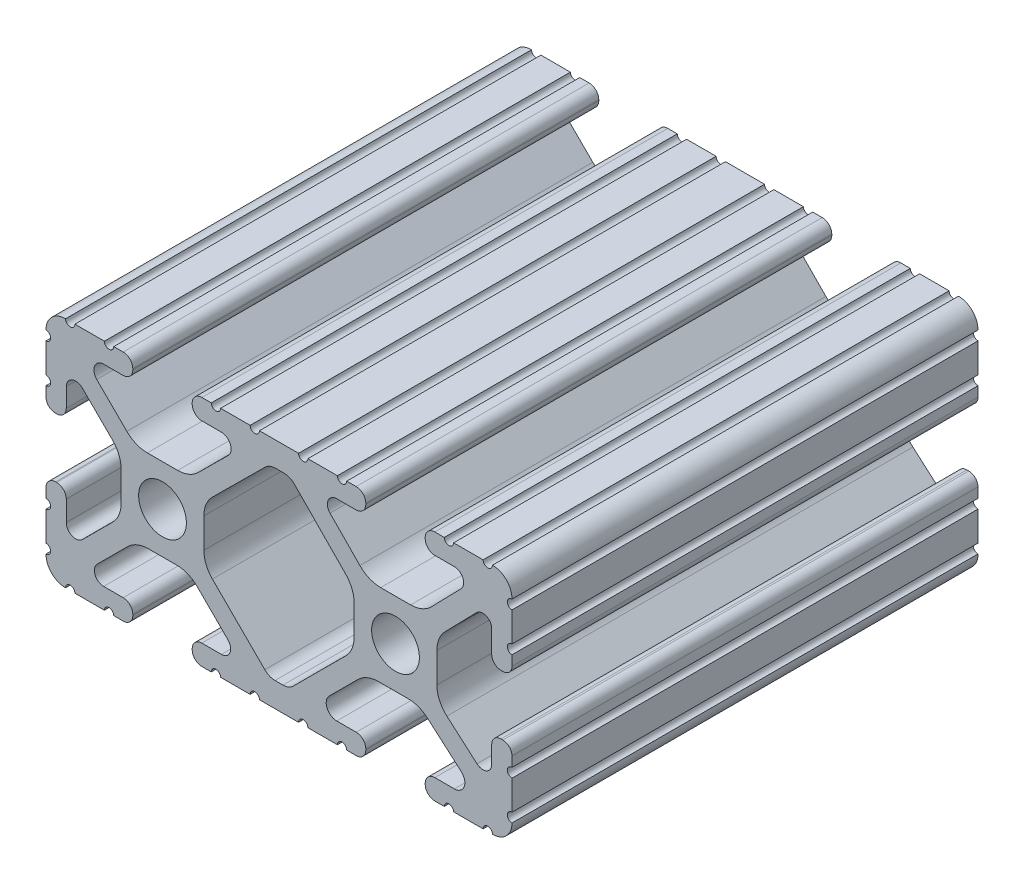
SolidWorks part; units mm, degrees
material "6061 Alloy"
ref_plane "Front Plane" through (0, 0, 0) normal (0, 0, 1) x (1, 0, 0)
ref_plane "Top Plane" through (0, 0, 0) normal (0, 1, 0) x (1, 0, 0)
ref_plane "Right Plane" through (0, 0, 0) normal (1, 0, 0) x (0, 0, -1)
sketch "Sketch1" plane through (0, 0, 0) normal (0, 0, 1) x (1, 0, 0)
  line L0 (-32.9707, 0) -> (32.2708, 0) construction
  line L1 (0, 12.7) -> (0, 0) construction
  line L2 (-12.7, 14.992) -> (-12.7, -12.6999) construction
  line L3 (12.7, 13.9801) -> (12.7, -13.3809) construction
  line L4 (-7.2595, -3.8694) -> (-1.5457, -9.5728)
  line L5 (1.5457, -9.5728) -> (7.2595, -3.8694)
  line L7 (-0.3952, 10.033) -> (0.5515, 10.033)
  line L9 (0.4332, -10.033) -> (-0.4332, -10.033)
  line L12 (8.1915, -1.6223) -> (8.1915, 1.6223)
  line L13 (7.2829, 3.8459) -> (1.6756, 9.5611)
  line L14 (-1.504, 9.5765) -> (-7.252, 3.8768)
  line L15 (-8.1915, 1.6223) -> (-8.1915, -1.6223)
  line L16 (22.2504, 12.7) -> (19.0331, 12.7)
  line L17 (18.0171, 12.7) -> (16.9875, 12.7)
  line L18 (15.9385, 11.651) -> (15.9385, 11.5392)
  line L19 (16.9875, 10.4902) -> (19.1164, 10.4902)
  line L20 (19.8441, 8.7652) -> (16.619, 5.4551)
  line L21 (14.3449, 4.4958) -> (11.0833, 4.4958)
  line L22 (8.817, 5.4472) -> (5.5642, 8.7627)
  line L23 (6.2894, 10.4902) -> (8.4125, 10.4902)
  line L24 (9.4615, 11.5392) -> (9.4615, 11.651)
  line L25 (8.4125, 12.7) -> (7.3829, 12.7)
  line L26 (6.3669, 12.7) -> (3.1496, 12.7)
  line L27 (2.1336, 12.7) -> (-2.1336, 12.7)
  line L28 (-3.1496, 12.7) -> (-6.3669, 12.7)
  line L29 (-7.3829, 12.7) -> (-8.4125, 12.7)
  line L30 (-9.4615, 11.651) -> (-9.4615, 11.5392)
  line L31 (-8.4125, 10.4902) -> (-6.2836, 10.4902)
  line L32 (-5.5326, 8.6661) -> (-8.81, 5.4163)
  line L33 (-11.0455, 4.4958) -> (-14.3545, 4.4958)
  line L34 (-16.59, 5.4163) -> (-19.8674, 8.6661)
  line L35 (-19.1164, 10.4902) -> (-16.9875, 10.4902)
  line L36 (-15.9385, 11.5392) -> (-15.9385, 11.651)
  line L37 (-16.9875, 12.7) -> (-18.0171, 12.7)
  line L38 (-19.0331, 12.7) -> (-22.2504, 12.7)
  line L39 (-25.4, 9.5504) -> (-25.4, 6.3331)
  line L40 (-25.4, 5.3171) -> (-25.4, 4.2375)
  line L41 (-24.401, 3.2385) -> (-24.2392, 3.2385)
  line L42 (-23.1902, 4.2875) -> (-23.1902, 6.3347)
  line L43 (-21.434, 7.0665) -> (-18.148, 3.8082)
  line L44 (-17.2085, 1.5536) -> (-17.2085, -1.6952)
  line L45 (-18.1405, -3.9423) -> (-21.4316, -7.2274)
  line L46 (-23.1902, -6.498) -> (-23.1902, -4.2875)
  line L47 (-24.2392, -3.2385) -> (-24.351, -3.2385)
  line L48 (-25.4, -4.2875) -> (-25.4, -5.3171)
  line L49 (-25.4, -6.3331) -> (-25.4, -9.5504)
  line L50 (-22.2504, -12.7) -> (-19.0331, -12.7)
  line L51 (-18.0171, -12.7) -> (-16.9875, -12.7)
  line L52 (-15.9384, -11.651) -> (-15.9384, -11.5392)
  line L53 (-16.9875, -10.4902) -> (-19.1164, -10.4902)
  line L54 (-19.8341, -8.7551) -> (-16.4966, -5.4237)
  line L55 (-14.2536, -4.4958) -> (-11.1464, -4.4958)
  line L56 (-8.9034, -5.4237) -> (-5.5659, -8.7551)
  line L57 (-6.2836, -10.4902) -> (-8.4125, -10.4902)
  line L58 (-9.4616, -11.5392) -> (-9.4616, -11.651)
  line L59 (-8.4125, -12.7) -> (-7.3829, -12.7)
  line L60 (-6.3669, -12.7) -> (-3.1496, -12.7)
  line L61 (-2.1336, -12.7) -> (2.1336, -12.7)
  line L62 (3.1496, -12.7) -> (6.3669, -12.7)
  line L63 (7.3829, -12.7) -> (8.4125, -12.7)
  line L64 (9.4616, -11.651) -> (9.4616, -11.5392)
  line L65 (8.4125, -10.4902) -> (6.2894, -10.4902)
  line L66 (5.4807, -8.5353) -> (8.5979, -5.4237)
  line L67 (10.8409, -4.4958) -> (14.1026, -4.4958)
  line L68 (16.1879, -5.2766) -> (19.8682, -8.4822)
  line L69 (19.1164, -10.4902) -> (16.9875, -10.4902)
  line L70 (15.9384, -11.5392) -> (15.9384, -11.651)
  line L71 (16.9875, -12.7) -> (18.0171, -12.7)
  line L72 (19.0331, -12.7) -> (22.2504, -12.7)
  line L73 (25.4, -9.5504) -> (25.4, -6.3331)
  line L74 (25.4, -5.3171) -> (25.4, -4.2375)
  line L75 (24.401, -3.2385) -> (24.1892, -3.2385)
  line L76 (23.1902, -4.2375) -> (23.1902, -6.1559)
  line L77 (21.584, -6.8869) -> (18.2982, -4.025)
  line L78 (17.2085, -1.6308) -> (17.2085, 1.6308)
  line L79 (18.1094, 3.8465) -> (21.5263, 7.3534)
  line L80 (23.1902, 6.6769) -> (23.1902, 4.2375)
  line L81 (24.1892, 3.2385) -> (24.401, 3.2385)
  line L82 (25.4, 4.2375) -> (25.4, 5.3171)
  line L83 (25.4, 6.3332) -> (25.4, 9.5504)
  circle A0 centre (-12.7, 0) radius 2.6035
  circle A1 centre (12.7, 0) radius 2.6035
  arc A2 (-0.3952, 10.033) -> (-1.504, 9.5765) centre (-0.3952, 8.4582) ccw
  arc A3 (0.5515, 10.033) -> (1.6756, 9.5611) centre (0.5515, 8.4582) cw
  arc A4 (-8.1915, -1.6223) -> (-7.2595, -3.8694) centre (-5.0165, -1.6223) ccw
  arc A5 (-0.4332, -10.033) -> (-1.5457, -9.5728) centre (-0.4332, -8.4582) cw
  arc A6 (7.2595, -3.8694) -> (8.1915, -1.6223) centre (5.0165, -1.6223) ccw
  arc A7 (8.1915, 1.6223) -> (7.2829, 3.8459) centre (5.0165, 1.6223) ccw
  arc A8 (0.4332, -10.033) -> (1.5457, -9.5728) centre (0.4332, -8.4582) ccw
  arc A9 (-7.252, 3.8768) -> (-8.1915, 1.6223) centre (-5.0165, 1.6223) ccw
  arc A16 (25.3998, 10.5664) -> (23.2664, 12.6998) centre (23.2918, 10.5918) ccw
  arc A17 (22.2504, 12.7) -> (23.2664, 12.6998) centre (22.7584, 12.7) ccw
  arc A18 (18.0171, 12.7) -> (19.0331, 12.7) centre (18.5251, 12.7) ccw
  arc A19 (16.9875, 12.7) -> (15.9385, 11.651) centre (16.9875, 11.651) ccw
  arc A20 (15.9385, 11.5392) -> (16.9875, 10.4902) centre (16.9875, 11.5392) ccw
  arc A21 (19.8441, 8.7652) -> (19.1164, 10.4902) centre (19.1164, 9.4742) ccw
  arc A22 (14.3449, 4.4958) -> (16.619, 5.4551) centre (14.3449, 7.6708) ccw
  arc A23 (8.817, 5.4472) -> (11.0833, 4.4958) centre (11.0833, 7.6708) ccw
  arc A24 (6.2894, 10.4902) -> (5.5642, 8.7627) centre (6.2894, 9.4742) ccw
  arc A25 (8.4125, 10.4902) -> (9.4615, 11.5392) centre (8.4125, 11.5392) ccw
  arc A26 (9.4615, 11.651) -> (8.4125, 12.7) centre (8.4125, 11.651) ccw
  arc A27 (6.3669, 12.7) -> (7.3829, 12.7) centre (6.8749, 12.7) ccw
  arc A28 (2.1336, 12.7) -> (3.1496, 12.7) centre (2.6416, 12.7) ccw
  arc A29 (-3.1496, 12.7) -> (-2.1336, 12.7) centre (-2.6416, 12.7) ccw
  arc A30 (-7.3829, 12.7) -> (-6.3669, 12.7) centre (-6.8749, 12.7) ccw
  arc A31 (-8.4125, 12.7) -> (-9.4615, 11.651) centre (-8.4125, 11.651) ccw
  arc A32 (-9.4615, 11.5392) -> (-8.4125, 10.4902) centre (-8.4125, 11.5392) ccw
  arc A33 (-5.5326, 8.6661) -> (-6.2836, 10.4902) centre (-6.2836, 9.4235) ccw
  arc A34 (-11.0455, 4.4958) -> (-8.81, 5.4163) centre (-11.0455, 7.6708) ccw
  arc A35 (-16.59, 5.4163) -> (-14.3545, 4.4958) centre (-14.3545, 7.6708) ccw
  arc A36 (-19.1164, 10.4902) -> (-19.8674, 8.6661) centre (-19.1164, 9.4235) ccw
  arc A37 (-16.9875, 10.4902) -> (-15.9385, 11.5392) centre (-16.9875, 11.5392) ccw
  arc A38 (-15.9385, 11.651) -> (-16.9875, 12.7) centre (-16.9875, 11.651) ccw
  arc A39 (-19.0331, 12.7) -> (-18.0171, 12.7) centre (-18.5251, 12.7) ccw
  arc A40 (-23.2664, 12.6998) -> (-22.2504, 12.7) centre (-22.7584, 12.7) ccw
  arc A41 (-23.2664, 12.6998) -> (-25.3998, 10.5664) centre (-23.2918, 10.5918) ccw
  arc A42 (-25.4, 9.5504) -> (-25.3998, 10.5664) centre (-25.4, 10.0584) ccw
  arc A43 (-25.4, 5.3171) -> (-25.4, 6.3331) centre (-25.4, 5.8251) ccw
  arc A44 (-25.4, 4.2375) -> (-24.401, 3.2385) centre (-24.401, 4.2375) ccw
  arc A45 (-24.2392, 3.2385) -> (-23.1902, 4.2875) centre (-24.2392, 4.2875) ccw
  arc A46 (-21.434, 7.0665) -> (-23.1902, 6.3347) centre (-22.1596, 6.3347) ccw
  arc A47 (-17.2085, 1.5536) -> (-18.148, 3.8082) centre (-20.3835, 1.5536) ccw
  arc A48 (-18.1405, -3.9423) -> (-17.2085, -1.6952) centre (-20.3835, -1.6952) ccw
  arc A49 (-23.1902, -6.498) -> (-21.4316, -7.2274) centre (-22.1596, -6.498) ccw
  arc A50 (-23.1902, -4.2875) -> (-24.2392, -3.2385) centre (-24.2392, -4.2875) ccw
  arc A51 (-24.351, -3.2385) -> (-25.4, -4.2875) centre (-24.351, -4.2875) ccw
  arc A52 (-25.4, -6.3331) -> (-25.4, -5.3171) centre (-25.4, -5.8251) ccw
  arc A53 (-25.3998, -10.5664) -> (-25.4, -9.5504) centre (-25.4, -10.0584) ccw
  arc A54 (-25.3998, -10.5664) -> (-23.2664, -12.6998) centre (-23.2918, -10.5918) ccw
  arc A55 (-22.2504, -12.7) -> (-23.2664, -12.6998) centre (-22.7584, -12.7) ccw
  arc A56 (-18.0171, -12.7) -> (-19.0331, -12.7) centre (-18.5251, -12.7) ccw
  arc A57 (-16.9875, -12.7) -> (-15.9384, -11.651) centre (-16.9875, -11.651) ccw
  arc A58 (-15.9384, -11.5392) -> (-16.9875, -10.4902) centre (-16.9875, -11.5392) ccw
  arc A59 (-19.8341, -8.7551) -> (-19.1164, -10.4902) centre (-19.1164, -9.4742) ccw
  arc A60 (-14.2536, -4.4958) -> (-16.4966, -5.4237) centre (-14.2536, -7.6708) ccw
  arc A61 (-8.9034, -5.4237) -> (-11.1464, -4.4958) centre (-11.1464, -7.6708) ccw
  arc A62 (-6.2836, -10.4902) -> (-5.5659, -8.7551) centre (-6.2836, -9.4742) ccw
  arc A63 (-8.4125, -10.4902) -> (-9.4616, -11.5392) centre (-8.4125, -11.5392) ccw
  arc A64 (-9.4616, -11.651) -> (-8.4125, -12.7) centre (-8.4125, -11.651) ccw
  arc A65 (-6.3669, -12.7) -> (-7.3829, -12.7) centre (-6.8749, -12.7) ccw
  arc A66 (-2.1336, -12.7) -> (-3.1496, -12.7) centre (-2.6416, -12.7) ccw
  arc A67 (3.1496, -12.7) -> (2.1336, -12.7) centre (2.6416, -12.7) ccw
  arc A68 (7.3829, -12.7) -> (6.3669, -12.7) centre (6.8749, -12.7) ccw
  arc A69 (8.4125, -12.7) -> (9.4616, -11.651) centre (8.4125, -11.651) ccw
  arc A70 (9.4616, -11.5392) -> (8.4125, -10.4902) centre (8.4125, -11.5392) ccw
  arc A71 (5.4807, -8.5353) -> (6.2894, -10.4902) centre (6.2894, -9.3455) ccw
  arc A72 (10.8409, -4.4958) -> (8.5979, -5.4237) centre (10.8409, -7.6708) ccw
  arc A73 (16.1879, -5.2766) -> (14.1026, -4.4958) centre (14.1026, -7.6708) ccw
  arc A74 (19.1164, -10.4902) -> (19.8682, -8.4822) centre (19.1164, -9.3455) ccw
  arc A75 (16.9875, -10.4902) -> (15.9384, -11.5392) centre (16.9875, -11.5392) ccw
  arc A76 (15.9384, -11.651) -> (16.9875, -12.7) centre (16.9875, -11.651) ccw
  arc A77 (19.0331, -12.7) -> (18.0171, -12.7) centre (18.5251, -12.7) ccw
  arc A78 (23.2664, -12.6998) -> (22.2504, -12.7) centre (22.7584, -12.7) ccw
  arc A79 (23.2664, -12.6998) -> (25.3998, -10.5664) centre (23.2918, -10.5918) ccw
  arc A80 (25.4, -9.5504) -> (25.3998, -10.5664) centre (25.4, -10.0584) ccw
  arc A81 (25.4, -5.3171) -> (25.4, -6.3331) centre (25.4, -5.8251) ccw
  arc A82 (25.4, -4.2375) -> (24.401, -3.2385) centre (24.401, -4.2375) ccw
  arc A83 (24.1892, -3.2385) -> (23.1902, -4.2375) centre (24.1892, -4.2375) ccw
  arc A84 (21.584, -6.8869) -> (23.1902, -6.1559) centre (22.2207, -6.1559) ccw
  arc A85 (17.2085, -1.6308) -> (18.2982, -4.025) centre (20.3835, -1.6308) ccw
  arc A86 (18.1094, 3.8465) -> (17.2085, 1.6308) centre (20.3835, 1.6308) ccw
  arc A87 (23.1902, 6.6769) -> (21.5263, 7.3534) centre (22.2207, 6.6769) ccw
  arc A88 (23.1902, 4.2375) -> (24.1892, 3.2385) centre (24.1892, 4.2375) ccw
  arc A89 (24.401, 3.2385) -> (25.4, 4.2375) centre (24.401, 4.2375) ccw
  arc A90 (25.4, 6.3332) -> (25.4, 5.3171) centre (25.4, 5.8251) ccw
  arc A91 (25.3998, 10.5664) -> (25.4, 9.5504) centre (25.4, 10.0584) ccw
  dimension "D1" = 5.207
  dimension "D6" = 6.477
  dimension "D7" = 14.859
  dimension "D14" = 1.5748
  dimension "D16" = 1.5748
  dimension "D15" = 3.175
  dimension "D2" = 25.4
  dimension "D3" = 50.8
  dimension "D4" = 25.4
  dimension "D5" = 8.2042
  dimension "D8" = 2.2098
  dimension "D9" = 2.2098
  dimension "D10" = 2.2098
  dimension "D11" = 2.2098
  dimension "D12" = 2.2098
  dimension "D13" = 6.477
extrude "Extrude1" add sketch "Sketch1" against normal blind 50.8
